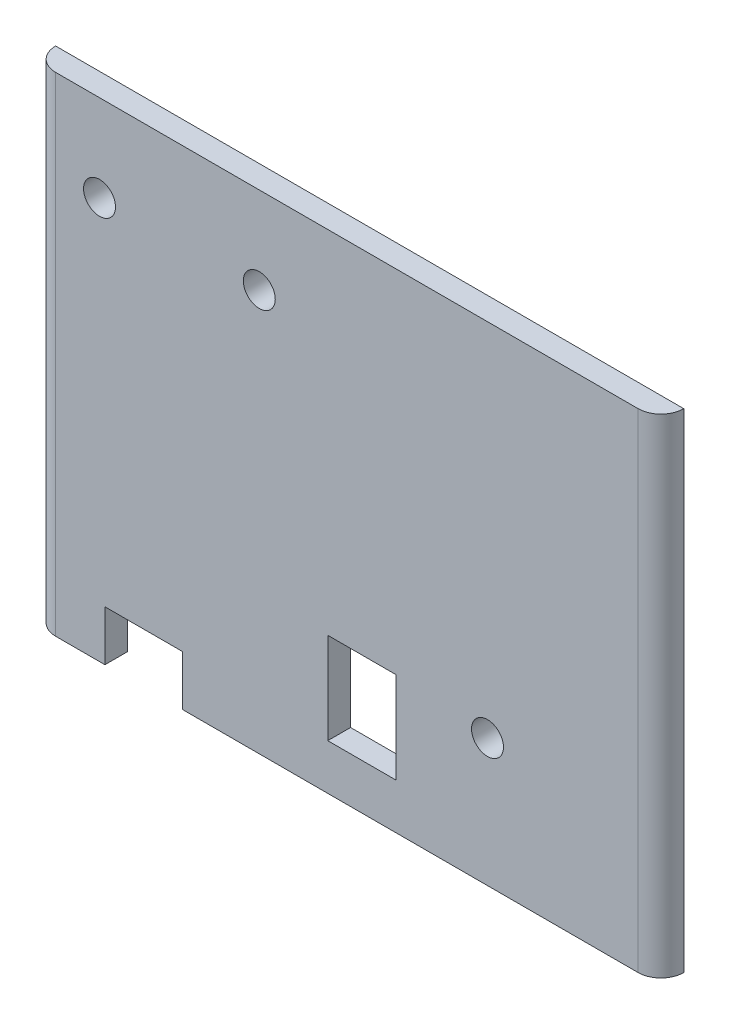
SolidWorks part; units mm, degrees
note: The reader was unsure of these and kept them because the rebuilt part matched: shared geometry of "Sketch21<2>".
ref_plane "Front Plane" through (0, 0, 0) normal (0, 0, 1) x (1, 0, 0)
ref_plane "Top Plane" through (0, 0, 0) normal (0, 1, 0) x (1, 0, 0)
ref_plane "Right Plane" through (0, 0, 0) normal (1, 0, 0) x (0, 0, -1)
sketch "Sketch1" plane through (0, 0, 0) normal (0, 0, 1) x (1, 0, 0)
  line L0 (0, 0) -> (0, 135)
  line L11 (0, 135) -> (150, 135)
  line L12 (150, 135) -> (150, 0)
  line L13 (150, 0) -> (0, 0)
  circle A0 centre (20, 116) radius 2.1
  circle A1 centre (55, 116) radius 2.1
  circle A2 centre (105, 56) radius 2.1
  dimension "D1" = 4.2
  dimension "D2" = 135
  dimension "D5" = 150
extrude "Boss-Extrude2" add sketch "Sketch1" along normal blind 70
sketch "Sketch13" plane through (0, 0, 0) normal (0, 0, -1) x (-1, 0, 0)
  line L1 (-159.5351, 142.4206) -> (6.6327, 142.4206)
  line L2 (-159.5351, 142.4206) -> (-159.5351, -6.5136)
  line L3 (-159.5351, -6.5136) -> (6.6327, -6.5136)
  line L4 (6.6327, 142.4206) -> (6.6327, -6.5136)
extrude "Cut-Extrude1" cut sketch "Sketch13" against normal blind 60
sketch "Sketch17" plane through (0, 0, 70) normal (0, 0, 1) x (1, 0, 0)
  line L0 (46.6506, 29) -> (12.7094, 29) construction
  line L1 (21.18, 28) -> (38.18, 28)
  line L2 (21.18, 28) -> (21.18, 39)
  line L3 (21.18, 39) -> (38.18, 39)
  line L4 (38.18, 28) -> (38.18, 39)
  line L5 (29.68, 29) -> (29.68, 33.8908) construction
  line L6 (65, 51) -> (65, 28) construction
  line L7 (70, 38) -> (85, 38)
  line L8 (70, 38) -> (70, 58)
  line L9 (70, 58) -> (85, 58)
  line L10 (85, 38) -> (85, 58)
  line L11 (-4, 28) -> (154, 28) construction
  dimension "D1" = 17
  dimension "D2" = 11
  dimension "D3" = 15
  dimension "D4" = 5
  dimension "D5" = 10
  dimension "D6" = 20
  dimension "D7" = 1
extrude "Cut-Extrude5" cut sketch "Sketch17" against normal blind 10
sketch "Sketch18" plane through (0, 0, 70) normal (0, 0, 1) x (1, 0, 0)
  line L0 (5.38, 28) -> (5.38, 135)
  line L5 (150, 135) -> (0, 135) construction
  line L6 (5.38, 135) -> (143, 135)
  line L7 (143, 135) -> (143, 28)
  line L8 (143, 28) -> (5.38, 28)
  line L9 (5.38, 135) -> (143, 135)
  line L10 (-20.0857, 157.1) -> (193.8571, 157.1)
  line L11 (193.8571, 157.1) -> (193.8571, -29.4143)
  line L12 (193.8571, -29.4143) -> (-16.4286, -29.4143)
  line L13 (-16.4286, -29.4143) -> (-20.0857, 157.1)
  line L14 (0, 135) -> (0, 0) construction
  line L15 (150, 0) -> (150, 135) construction
  line M21 (0, 0) -> (150, 0)
  line M22 (150, 0) -> (150, 135)
  line M23 (150, 135) -> (0, 135)
  line M24 (0, 135) -> (0, 0)
  dimension "D1" = 5.38
  dimension "D2" = 7
  dimension "D3" = 107
extrude "Cut-Extrude6" cut sketch "Sketch18" against normal through all both and the other way through all contours L13 L12 L11 L10 M21 M24 M23 M22 | L7 L8 L0 M23 M24 M21 M22
sketch "Sketch19" plane through (143, 0, 0) normal (1, 0, 0) x (0, 0, -1)
  line L0 (-65, 138.6228) -> (-65, 12.2478)
  line L1 (-65, 12.2478) -> (-38.7818, -5.101)
  line L2 (-38.7818, -5.101) -> (-31.8529, 142.6325)
  line L3 (-31.8529, 142.6325) -> (-65, 138.6228)
  line L4 (-70, 28) -> (-70, 135) construction
  dimension "D1" = 5
extrude "Cut-Extrude7" cut sketch "Sketch19" against normal through all both and the other way through all
fillet "Fillet1" radius 5 2 edges at (5.38, 81.5, 70) (143, 81.5, 70)
sketch "Sketch20" plane through (0, 0, 65) normal (0, 0, -1) x (-1, 0, 0)
  line L1 (-59, 112) -> (-51, 112)
  line L2 (-59, 112) -> (-59, 120)
  line L3 (-59, 120) -> (-51, 120)
  line L4 (-51, 112) -> (-51, 120)
  line L5 (-59, 112) -> (-51, 120) construction
  line L6 (-59, 120) -> (-51, 112) construction
  line L7 (-16, 120) -> (-24, 120)
  line L8 (-16, 120) -> (-16, 112)
  line L9 (-16, 112) -> (-24, 112)
  line L10 (-24, 120) -> (-24, 112)
  line L11 (-16, 120) -> (-24, 112) construction
  line L12 (-16, 112) -> (-24, 120) construction
  line L13 (-109, 52) -> (-101, 52)
  line L14 (-109, 52) -> (-109, 60)
  line L15 (-109, 60) -> (-101, 60)
  line L16 (-101, 52) -> (-101, 60)
  line L17 (-109, 52) -> (-101, 60) construction
  line L18 (-109, 60) -> (-101, 52) construction
  point P0 (-55, 116)
  point P6 (-20, 116)
  point P12 (-105, 56)
  dimension "D1" = 8
extrude "Boss-Extrude3" add sketch "Sketch20" along normal blind 3
sketch "Sketch21" plane through (0, 0, 70) normal (0, 0, 1) x (1, 0, 0)
  circle A0 centre (20, 116) radius 3.5
  circle A1 centre (55, 116) radius 3.5
  circle A2 centre (105, 56) radius 3.5
  circle A3 centre (20, 116) radius 2.1
  circle A4 centre (55, 116) radius 2.1
  circle A5 centre (105, 56) radius 2.1
  dimension "D1" = 4.2
  dimension "D2" = 7
extrude "Cut-Extrude9" cut sketch "Sketch21" against normal blind 5
extrude "Cut-Extrude10" cut sketch "Sketch21<2>" against normal through all both and the other way through all
sketch "Sketch21<2>" plane through (0, 0, 70) normal (0, 0, 1) x (1, 0, 0) same geometry as "Sketch21"
